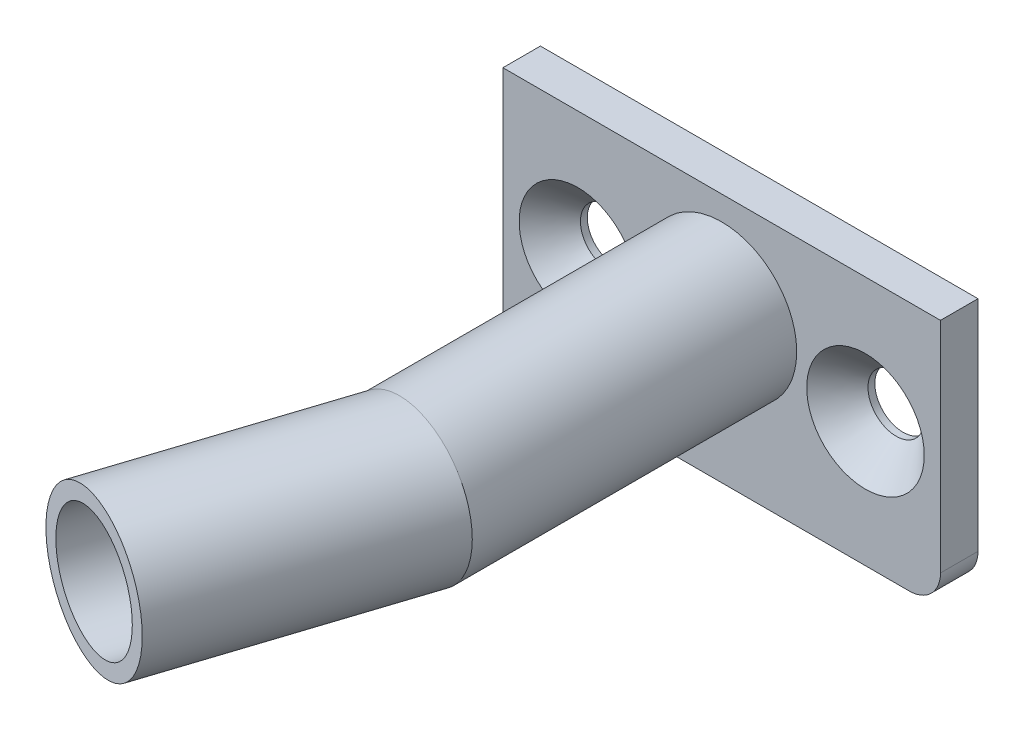
SolidWorks part; units mm, degrees
material "Ti-6Al-4VSolution treated and aged (SS)"
ref_plane "Top Plane" through (0, 0, 0) normal (0, 0, 1) x (1, 0, 0)
ref_plane "Front Plane" through (0, 0, 0) normal (0, 1, 0) x (1, 0, 0)
ref_plane "Right Plane" through (0, 0, 0) normal (1, 0, 0) x (0, 0, -1)
sketch "Sketch7" plane through (0, 0, 0) normal (0, 0, 1) x (1, 0, 0)
  line L1 (-17.5, -10) -> (17.5, -10)
  line L2 (-17.5, -10) -> (-17.5, 10)
  line L3 (-17.5, 10) -> (17.5, 10)
  line L4 (17.5, -10) -> (17.5, 10)
  line L5 (-17.5, -10) -> (17.5, 10) construction
  line L6 (-17.5, 10) -> (17.5, -10) construction
  point P0 (0, 0)
  dimension "D1" = 35
  dimension "D2" = 20
extrude "Boss-Extrude4" add sketch "Sketch7" along normal blind 3
fillet "Fillet1" radius 2.5 2 edges at (17.5, -10, 1.5) (-17.5, -10, 1.5)
sketch "Sketch8" plane through (0, 0, 3) normal (0, 0, 1) x (1, 0, 0)
  line L0 (-17.5, 1.25) -> (17.5, 1.25) construction
  line L1 (-17.5, 10) -> (-17.5, -7.5) construction
  line L2 (17.5, -7.5) -> (17.5, 10) construction
  line L3 (0, 10) -> (0, -10) construction
  line L4 (17.5, 10) -> (-17.5, 10) construction
  line L5 (-15, -10) -> (15, -10) construction
  circle A0 centre (0, 2.073) radius 6
  point P14 (0, 4.5468)
  dimension "D1" = 12
  dimension "D2" = 7.927
extrude "Boss-Extrude5" add sketch "Sketch8" along normal blind 20
ref_axis "Axis1" through (0, 2.073, 23) along (0, 0, -1)
ref_plane "Plane1" through (0, 2.073, 0) normal (0, 1, 0) x (1, 0, 0)
sketch "Sketch9" plane through (0, 2.073, 0) normal (0, 1, 0) x (1, 0, 0)
  line L0 (0, -23) -> (0, -28)
  line L1 (-6, -23) -> (6, -23) construction
  line L2 (0, -23) -> (0, -3) construction
  line L3 (0, -28) -> (-1.5451, -32.7553)
  dimension "D1" = 5
  dimension "D2" = 162
  dimension "D3" = 5
sketch "Sketch10" plane through (0, 0, 23) normal (0, 0, 1) x (1, 0, 0)
  circle A1 centre (0, 2.073) radius 6
  circle A2 centre (0, 2.073) radius 6
  dimension "D1" = 0
sweep "Sweep3" add profiles "Sketch10" path "Sketch9"
sketch "Sketch11" plane through (-9.7741, 0, 30.0815) normal (-0.309, 0, 0.9511) x (0.9511, 0, 0.309)
  circle A0 centre (8.6525, 2.073) radius 4.7625
  circle A1 centre (8.6525, 2.073) radius 6
  circle A2 centre (8.6525, 2.073) radius 6
  dimension "D2" = 9.525
  dimension "D1" = 0
extrude "Boss-Extrude6" add sketch "Sketch11" along normal blind 15
hole_wizard "CSK for M4 Flat Head Machine Screw1" positions "Sketch12" profile "Sketch13" countersink size "M4" standard "ANSI Metric" end condition through all
sketch "Sketch12" plane through (0, 0, 3) normal (0, 0, 1) x (1, 0, 0)
  point P0 (-11.5, 0)
  point P2 (11.5, 0)
  point P10 (-9.526, 0.1927)
  dimension "D1" = 11.5
  dimension "D2" = 11.5
sketch "Sketch13" plane through (-11.5, 0, 3) normal (1, 0, 0) x (0, -1, 0)
  line L0 (0, 0) -> (0, 3)
  line L1 (0, 3) -> (2.25, 3)
  line L2 (2.25, 3) -> (2.25, 2.45)
  line L3 (2.25, 2.45) -> (4.7, 0)
  line L5 (4.7, 0) -> (0, 0)
  line L6 (-2.25, 2.45) -> (-4.7, 0) construction
  line L11 (0, -6.35) -> (0, 107.95) construction
  dimension "Thru Hole Dia." = 4.5
  dimension "Thru Hole Depth" = 3
  dimension "Near C'Sink Dia." = 9.4
  dimension "Near C'Sink Angle" = 90
